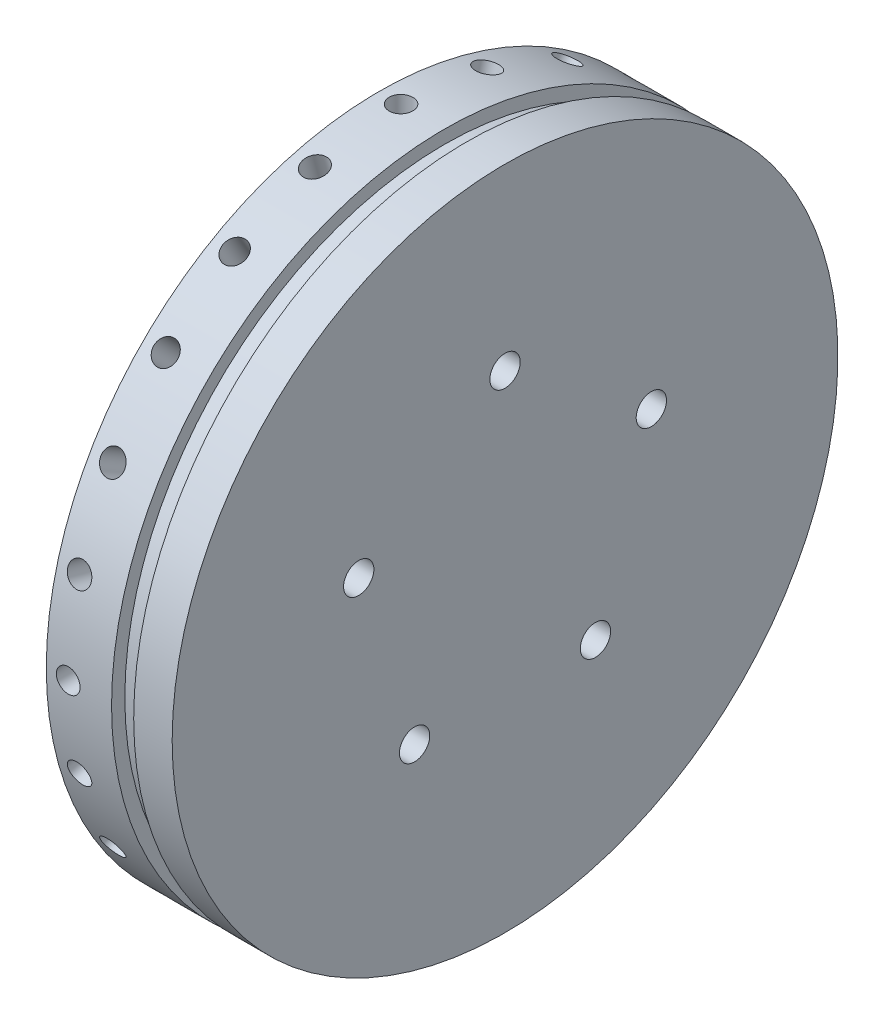
SolidWorks part; units mm, degrees
ref_plane "Front Plane" through (0, 0, 0) normal (0, 0, 1) x (1, 0, 0)
ref_plane "Top Plane" through (0, 0, 0) normal (0, 1, 0) x (1, 0, 0)
ref_plane "Right Plane" through (0, 0, 0) normal (1, 0, 0) x (0, 0, -1)
sketch "Cap Body Sketch" plane through (0, 0, 0) normal (0, 0, 1) x (1, 0, 0)
  line L0 (-1000, 0) -> (1000, 0) construction
  line L1 (13, 0) -> (13, 58)
  line L2 (13, 58) -> (8, 58)
  line L3 (8, 58) -> (8, 71.4)
  line L4 (8, 71.4) -> (22, 71.4)
  line L5 (22, 71.4) -> (22, 68.555)
  line L6 (22, 68.555) -> (26.75, 68.555)
  line L7 (26.75, 68.555) -> (26.75, 71.4)
  line L8 (26.75, 71.4) -> (35, 71.4)
  line L9 (35, 71.4) -> (35, 0)
  line L10 (35, 0) -> (13, 0)
revolve "Cap Body" add sketch "Cap Body Sketch" angle 360 about L0
ref_axis "Engine Axis" through (36.35, 0, 0) along (-1, 0, 0)
ref_plane "Port Face" through (13, 0, 0) normal (1, 0, 0) x (0, 0, -1)
sketch "Port 1 Thread Bore Sketch" plane through (13, 0, 0) normal (1, 0, 0) x (0, 0, -1)
  circle A0 centre (0, 33) radius 4.953
extrude "Port 1 Thread Bore" cut sketch "Port 1 Thread Bore Sketch" along normal blind 10.5
ref_plane "Port 1 Passage Plane" through (23.5, 0, 0) normal (1, 0, 0) x (0, 0, -1)
sketch "Port 1 Passage Sketch" plane through (23.5, 0, 0) normal (1, 0, 0) x (0, 0, -1)
  circle A0 centre (0, 33) radius 3.25
extrude "Port 1 Passage" cut sketch "Port 1 Passage Sketch" along normal blind 11.5
sketch "Port 2 Thread Bore Sketch" plane through (13, 0, 0) normal (1, 0, 0) x (0, 0, -1)
  circle A0 centre (31.3849, 10.1976) radius 4.953
extrude "Port 2 Thread Bore" cut sketch "Port 2 Thread Bore Sketch" along normal blind 10.5
ref_plane "Port 2 Passage Plane" through (23.5, 0, 0) normal (1, 0, 0) x (0, 0, -1)
sketch "Port 2 Passage Sketch" plane through (23.5, 0, 0) normal (1, 0, 0) x (0, 0, -1)
  circle A0 centre (31.3849, 10.1976) radius 3.25
extrude "Port 2 Passage" cut sketch "Port 2 Passage Sketch" along normal blind 11.5
sketch "Port 3 Thread Bore Sketch" plane through (13, 0, 0) normal (1, 0, 0) x (0, 0, -1)
  circle A0 centre (19.3969, -26.6976) radius 4.953
extrude "Port 3 Thread Bore" cut sketch "Port 3 Thread Bore Sketch" along normal blind 10.5
ref_plane "Port 3 Passage Plane" through (23.5, 0, 0) normal (1, 0, 0) x (0, 0, -1)
sketch "Port 3 Passage Sketch" plane through (23.5, 0, 0) normal (1, 0, 0) x (0, 0, -1)
  circle A0 centre (19.3969, -26.6976) radius 3.25
extrude "Port 3 Passage" cut sketch "Port 3 Passage Sketch" along normal blind 11.5
sketch "Port 4 Thread Bore Sketch" plane through (13, 0, 0) normal (1, 0, 0) x (0, 0, -1)
  circle A0 centre (-19.3969, -26.6976) radius 4.953
extrude "Port 4 Thread Bore" cut sketch "Port 4 Thread Bore Sketch" along normal blind 10.5
ref_plane "Port 4 Passage Plane" through (23.5, 0, 0) normal (1, 0, 0) x (0, 0, -1)
sketch "Port 4 Passage Sketch" plane through (23.5, 0, 0) normal (1, 0, 0) x (0, 0, -1)
  circle A0 centre (-19.3969, -26.6976) radius 3.25
extrude "Port 4 Passage" cut sketch "Port 4 Passage Sketch" along normal blind 11.5
sketch "Port 5 Thread Bore Sketch" plane through (13, 0, 0) normal (1, 0, 0) x (0, 0, -1)
  circle A0 centre (-31.3849, 10.1976) radius 4.953
extrude "Port 5 Thread Bore" cut sketch "Port 5 Thread Bore Sketch" along normal blind 10.5
ref_plane "Port 5 Passage Plane" through (23.5, 0, 0) normal (1, 0, 0) x (0, 0, -1)
sketch "Port 5 Passage Sketch" plane through (23.5, 0, 0) normal (1, 0, 0) x (0, 0, -1)
  circle A0 centre (-31.3849, 10.1976) radius 3.25
extrude "Port 5 Passage" cut sketch "Port 5 Passage Sketch" along normal blind 11.5
sketch "Screw Hole Sketch" plane through (0, 0, 0) normal (0, 0, 1) x (1, 0, 0)
  line L0 (12.7, 51.4) -> (12.7, 91.4) construction
  line L1 (12.7, 60.9) -> (15.25, 60.9)
  line L2 (15.25, 60.9) -> (15.25, 72.4)
  line L3 (15.25, 72.4) -> (12.7, 72.4)
  line L4 (12.7, 72.4) -> (12.7, 60.9)
revolve "Screw Hole" cut sketch "Screw Hole Sketch" angle 360 about L0
pattern_circular "Screw Holes x24" count 24 over 360 about axis through (36.35, 0, 0) along (-1, 0, 0) of "Screw Hole"
